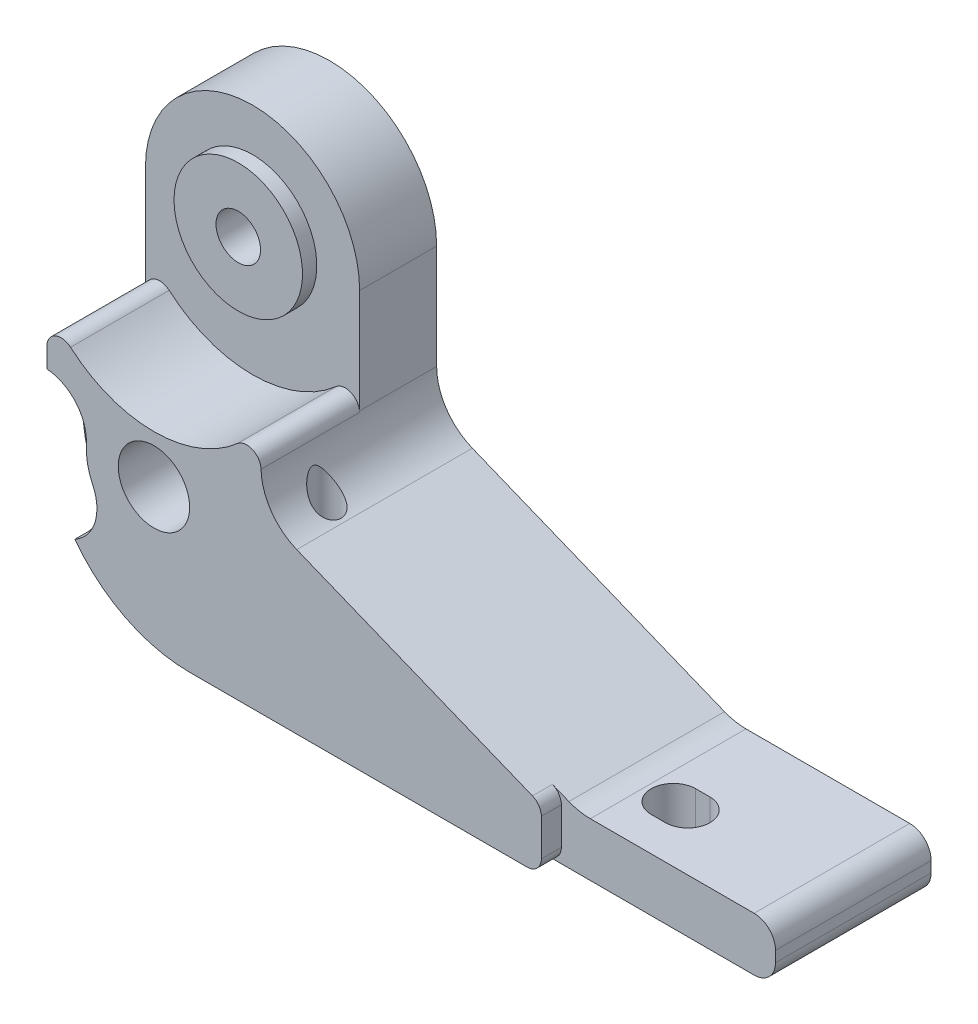
SolidWorks part; units mm, degrees
ref_plane "Front Plane" through (0, 0, 0) normal (0, 0, 1) x (1, 0, 0)
ref_plane "Top Plane" through (0, 0, 0) normal (0, 1, 0) x (1, 0, 0)
ref_plane "Right Plane" through (0, 0, 0) normal (1, 0, 0) x (0, 0, -1)
sketch "Sketch1" plane through (0, 0, 0) normal (0, 0, 1) x (1, 0, 0)
  line L0 (0, 15.5) -> (0, 0) construction
  line L1 (0, 0) -> (11, 0) construction
  line L2 (11, 0) -> (12.75, 0) construction
  line L3 (12.75, 0) -> (16.25, 0) construction
  line L4 (16.25, 0) -> (40.8118, 0) construction
  line L5 (40.8118, 0) -> (40.8118, 34.0698) construction
  line L6 (-9.525, 0) -> (-9.525, 28.2)
  line L7 (-9.525, 28.2) -> (53.5118, 28.2)
  line L8 (53.5118, 28.2) -> (53.5118, 23.4375)
  line L9 (9.525, 12.7) -> (36.0493, 23.4375)
  line L10 (9.525, 12.7) -> (9.525, 0)
  line L11 (36.0493, 23.4375) -> (53.5118, 23.4375)
  circle A0 centre (0, 0) radius 1.9812
  circle A1 centre (0, 15.5) radius 3.175
  circle A2 centre (0, 0) radius 11 construction
  circle A3 centre (16.25, 0) radius 3.5 construction
  arc A4 (-9.525, 0) -> (9.525, 0) centre (0, 0) ccw
  dimension "D1" = 3.9624
  dimension "D2" = 22
  dimension "D3" = 6.35
  dimension "D5" = 7
  dimension "D8" = 19.05
  dimension "D4" = 15.5
  dimension "D6" = 1.75
  dimension "D7" = 24.5618
  dimension "D9" = 12.7
  dimension "D10" = 4.7625
  dimension "D11" = 12.7
  dimension "D12" = 12.7
  dimension "D13" = 4.7625
extrude "Boss-Extrude1" add sketch "Sketch1" along normal blind 15.621
fillet "Fillet1" radius 5.08 2 edges at (36.0493, 23.4375, 7.8105) (9.525, 12.7, 7.8105)
fillet "Fillet2" radius 1.905 2 edges at (53.5118, 23.4375, 7.8105) (53.5118, 28.2, 7.8105)
sketch "Sketch2" plane through (0, 0, 0) normal (0, 0, -1) x (-1, 0, 0)
  circle A0 centre (0, 0) radius 11.25
  dimension "D1" = 22.5
extrude "Cut-Extrude1" cut sketch "Sketch2" against normal blind 8.77
sketch "Sketch3" plane through (0, 0, 8.77) normal (0, 0, -1) x (-1, 0, 0)
  circle A0 centre (0, 0) radius 5.715
  circle A1 centre (0, 0) radius 1.9812
  circle A2 centre (0, 0) radius 1.9812 construction
  dimension "D1" = 11.43
extrude "Boss-Extrude2" add sketch "Sketch3" along normal blind 1.27
fillet "Fillet3" radius 1.27 2 edges at (-9.525, 5.9864, 4.385) (9.525, 5.9864, 4.385)
move or copy body "Body-Move/Copy1" bodies to move or copy 103 copy no rotation origin (0, 6.7975, 6.35) rotation axis (1, 0, 0) rotation angle 180
sketch "Sketch4" plane through (0, -14.605, 0) normal (0, -1, 0) x (1, 0, 0)
  line L0 (51.6068, 12.7) -> (-9.525, 12.7) construction
  line L1 (34.4618, 12.7) -> (53.5118, 12.7)
  line L2 (34.4618, 12.7) -> (34.4618, 10.922)
  line L3 (34.4618, 10.922) -> (53.5118, 10.922)
  line L4 (53.5118, 12.7) -> (53.5118, 10.922)
  line L5 (53.5118, 12.7) -> (53.5118, -2.921) construction
  dimension "D1" = 1.778
  dimension "D2" = 19.05
extrude "Cut-Extrude2" cut sketch "Sketch4" against normal through all
fillet "Fillet4" radius 1.27 2 edges at (34.4618, -14.605, 11.811) (34.4618, -9.1999, 11.811)
fillet "Fillet5" radius 12.7 1 edges at (-9.525, -14.605, 4.8895)
sketch "Sketch5" plane through (0, 0, 12.7) normal (0, 0, 1) x (1, 0, 0)
  line L1 (-9.6492, -3.81) -> (0, -1.905) construction
  arc A2 (-5.4089, 0.7502) -> (-3.9939, -6.4166) centre (0, -1.905) ccw
  arc A3 (-5.4089, 0.7502) -> (-3.9939, -6.4166) centre (-9.6492, -3.81) ccw
  point P1 (-5.9113, -3.0721)
  dimension "D1" = 3.81
  dimension "D2" = 12.4541
extrude "Cut-Extrude3" cut sketch "Sketch5" against normal blind 3.175
sketch "Sketch6" plane through (0, -14.605, 0) normal (0, -1, 0) x (1, 0, 0)
  line L0 (41.8295, 14.7955) -> (38.2735, 14.7955) construction
  line L1 (41.8295, 13.208) -> (41.8295, 16.383) construction
  line L2 (38.2735, 16.383) -> (38.2735, 13.208) construction
  line L3 (38.2735, 14.7955) -> (40.0515, 14.7955) construction
  line L4 (40.0515, 14.7955) -> (40.0515, 5.9055) construction
  line L6 (39.4165, 5.9055) -> (40.6865, 5.9055) construction
  line L7 (39.4165, 7.8867) -> (40.6865, 7.8867)
  line L8 (39.4165, 3.9243) -> (40.6865, 3.9243)
  circle A0 centre (11.125, 8.4455) radius 1.27
  circle A1 centre (40.0515, 5.9055) radius 1.9812 construction
  arc A2 (39.4165, 7.8867) -> (39.4165, 3.9243) centre (39.4165, 5.9055) ccw
  arc A3 (40.6865, 3.9243) -> (40.6865, 7.8867) centre (40.6865, 5.9055) ccw
  point P17 (40.0515, 5.9055)
  dimension "D1" = 2.54
  dimension "D3" = 3.9624
  dimension "D2" = 8.89
  dimension "D4" = 1.27
extrude "Cut-Extrude4" cut sketch "Sketch6" against normal through all
fillet "Fillet6" radius 3.81 2 edges at (-5.4089, 0.7502, 11.1125) (-3.9939, -6.4166, 11.1125)
fillet "Fillet7" radius 2.032 3 edges at (-5.2536, -7.292, 9.525) (-5.9108, -3.075, 9.525) (-6.9569, 1.1293, 9.525)
sketch "Sketch7" plane through (0, -14.605, 0) normal (0, -1, 0) x (1, 0, 0)
  circle A0 centre (11.125, 8.4455) radius 2.54
  dimension "D1" = 5.08
extrude "Cut-Extrude5" cut sketch "Sketch7" against normal blind 8.89
